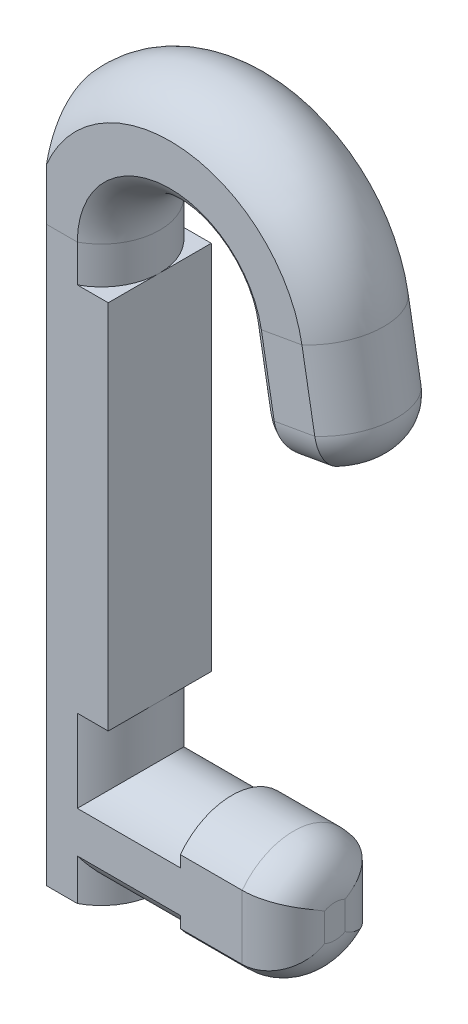
SolidWorks part; units mm, degrees
ref_plane "前视基准面" through (0, 0, 0) normal (0, 0, 1) x (1, 0, 0)
ref_plane "上视基准面" through (0, 0, 0) normal (0, 1, 0) x (1, 0, 0)
ref_plane "右视基准面" through (0, 0, 0) normal (1, 0, 0) x (0, 0, -1)
other "Configuration Table"
sketch "草图1" plane through (0, 0, 0) normal (0, 0, 1) x (1, 0, 0)
  line L0 (0, 0) -> (0, 24.8)
  line L1 (10.9164, 25.7551) -> (11.8862, 20.2551)
  line L2 (0, 0) -> (0, -3)
  arc A0 (0, 24.8) -> (10.9164, 25.7551) centre (5.5, 24.8) cw
  dimension "D1" = 5.5
  dimension "D2" = 10
  dimension "D3" = 24.8
  dimension "6" = 5.5
ref_plane "基准面3" through (0, -3, 0) normal (0, 1, 0) x (1, 0, 0)
sketch "草图13" plane through (0, -3, 0) normal (0, 1, 0) x (1, 0, 0)
  line L1 (-1, -2.5) -> (1, -2.5)
  line L3 (-1, 2.5) -> (1, 2.5)
  line L5 (-1, -2.5) -> (1, 2.5) construction
  line L6 (-1, 2.5) -> (1, -2.5) construction
  line L7 (0, 2.5) -> (0, -2.5) construction
  line L8 (1, 2.5) -> (1, -2.5) construction
  arc A0 (1, 2.5) -> (1, -2.5) centre (-0.3333, 0) cw
  arc A1 (-1, 2.5) -> (-1, -2.5) centre (0.3333, 0) ccw
  point P11 (1, 0)
  point P12 (2.5, 0)
  point P21 (0, 0)
  dimension "D2" = 2
  dimension "D1" = 5
  dimension "D3" = 1.5
sweep "扫描2" add profiles "草图13" path "草图1"
sketch "草图15" plane through (0, 0, 0) normal (0, 0, 1) x (1, 0, 0)
  line L0 (10.9164, 25.7551) -> (11.8862, 20.2551) construction
  line L1 (0, 0) -> (0, 24.8) construction
  line L3 (10.9164, 25.7551) -> (11.8862, 20.2551) construction
  line L4 (0, 0) -> (0, 24.8) construction
  line L5 (0, 0) -> (11, 0)
  arc A0 (10.9164, 25.7551) -> (0, 24.8) centre (5.5, 24.8) ccw construction
  arc A2 (10.9164, 25.7551) -> (0, 24.8) centre (5.5, 24.8) ccw construction
  dimension "D1" = 11
ref_plane "基准面2" through (11, 0, 0) normal (1, 0, 0) x (0, 0, -1)
sketch "草图16" plane through (11, 0, 0) normal (1, 0, 0) x (0, 0, -1)
  line L2 (-2.5, 0) -> (2.5, 0) construction
  line L4 (-2.5, -1) -> (-2.5, 1)
  line L6 (2.5, -1) -> (2.5, 1)
  line L7 (-2.5, -1) -> (2.5, 1) construction
  line L8 (-2.5, 1) -> (2.5, -1) construction
  line L9 (-2.5, -1) -> (2.5, -1) construction
  arc A3 (-2.5, -1) -> (2.5, -1) centre (0, 0.3333) ccw
  arc A4 (-2.5, 1) -> (2.5, 1) centre (0, -0.3333) cw
  point P0 (0, 0)
  point P9 (0, -2.5)
  dimension "D1" = 2
  dimension "D2" = 1.5
  dimension "D3" = 5
sweep "扫描4" add profiles "草图16" path "草图15"
sketch "草图17" plane through (11, 0, 0) normal (1, 0, 0) x (0, 0, -1)
  line L0 (-2.5, 1) -> (-2.5, -1) construction
  line L1 (-2.5, 1.5555) -> (-2.5, -1.5555)
  line L2 (2.5, -1) -> (2.5, 1) construction
  line L3 (2.5, -1) -> (2.5, 1) construction
  line L6 (2.5, 1.5555) -> (2.5, -1.5555)
  line L7 (2.5, 24.8) -> (2.5, 0) construction
  line L10 (-2.8, 1.073) -> (-2.8, -1.073)
  line L11 (2.8, -1.073) -> (2.8, 1.073)
  line L12 (-2.5, 0) -> (2.5, 0) construction
  arc A0 (2.5, -1.5555) -> (-2.5, -1.5555) centre (0, 0.3333) cw
  arc A15 (2.8, 1.073) -> (-2.8, 1.073) centre (0, -0.3333) ccw
  arc A16 (-2.8, -1.073) -> (2.8, -1.073) centre (0, 0.3333) ccw
  arc A17 (2.5, 1.5555) -> (-2.5, 1.5555) centre (0, -0.3333) ccw
  dimension "D1" = 0.3
extrude "凸台-拉伸1" add sketch "草图17" against normal blind 5
ref_plane "基准面4" through (1, 0, 0) normal (1, 0, 0) x (0, 0, -1)
sketch "草图19" plane through (1, 0, 0) normal (1, 0, 0) x (0, 0, -1)
  line L1 (-2.5, 5) -> (2.5, 5)
  line L2 (2.5, 0) -> (2.5, 24.8)
  line L3 (-2.5, 24.8) -> (-2.5, 0)
  line L4 (2.5, 5) -> (2.5, 23)
  line L5 (-2.5, 23) -> (-2.5, 5)
  line L6 (-2.5, 23) -> (2.5, 23)
  line L7 (0, 0) -> (0, 23) construction
  line L11 (2.5, 24.8) -> (-2.5, 24.8)
  line L12 (-2.5, 0) -> (2.5, 0)
  dimension "D2" = 18
  dimension "D3" = 5
  dimension "D1" = 0
extrude "凸台-拉伸2" add sketch "草图19" along normal blind 1.5
fillet "圆角2" radius 2 8 edges at (11.8862, 20.2551, 2.5) (14.3483, 20.6892, 0) (11.8862, 20.2551, -2.5) (9.4242, 19.8209, 0) (11, -2.8, 0) (11, 0, 2.5) (11, 2.8, 0) (11, 0, -2.5)
ref_plane "基准面5" through (-0.5, 0, 0) normal (1, 0, 0) x (0, 0, -1)
sketch "草图20" plane through (-0.5, 0, 0) normal (1, 0, 0) x (0, 0, -1)
  line L1 (4, -4) -> (-4, -4)
  line L2 (4, -4) -> (4, 36)
  line L3 (4, 36) -> (-4, 36)
  line L4 (-4, -4) -> (-4, 36)
  point P6 (-4.968, -3.5996)
  dimension "D1" = 4
  dimension "D2" = 4
  dimension "D3" = 4
  dimension "D4" = 40
extrude "切除-拉伸1" cut sketch "草图20" against normal through all
